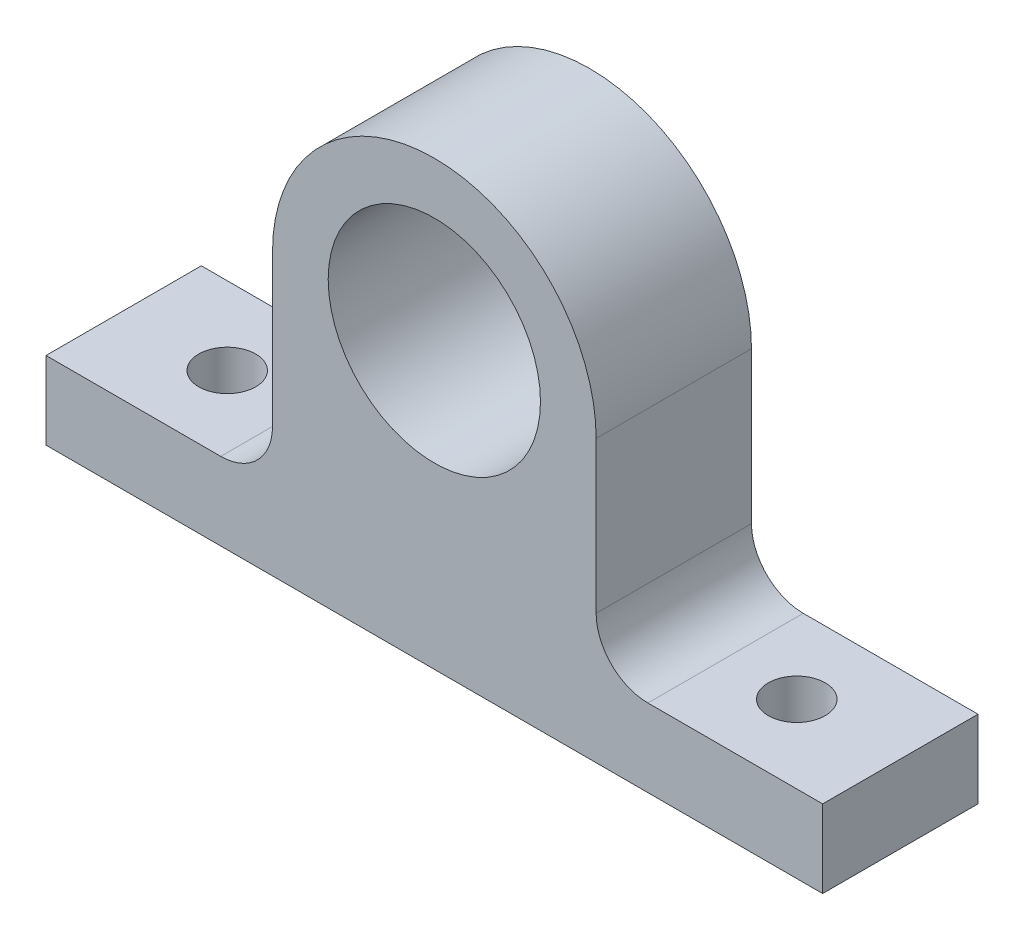
SolidWorks part; units mm, degrees
ref_plane "Front Plane" through (0, 0, 0) normal (0, 0, 1) x (1, 0, 0)
ref_plane "Top Plane" through (0, 0, 0) normal (0, 1, 0) x (1, 0, 0)
ref_plane "Right Plane" through (0, 0, 0) normal (1, 0, 0) x (0, 0, -1)
sketch "Sketch2" plane through (0, 0, 0) normal (0, 0, 1) x (1, 0, 0)
  line L0 (6.25, -8) -> (15, -8)
  line L1 (-6.25, 6.1) -> (6.25, 6.1)
  line L2 (-6.25, 6.1) -> (-6.25, -8)
  line L4 (6.25, 6.1) -> (6.25, -8)
  line L5 (-15, -11) -> (15, -11)
  line L6 (-15, -11) -> (-15, -8)
  line L7 (-15, -8) -> (-6.25, -8)
  line L8 (15, -11) -> (15, -8)
  circle A0 centre (0, 0) radius 4.1
  point P4 (0, 6.1)
  point P5 (0, -11)
  dimension "D1" = 6.1
  dimension "8.2" = 8.2
  dimension "D2" = 30
  dimension "D3" = 3
  dimension "D4" = 12.5
  dimension "D5" = 11
extrude "Boss-Extrude1" add sketch "Sketch2" along normal mid plane 6
fillet "Fillet1" 2 edges at (6.25, 6.1, 0) (-6.25, 6.1, 0) type full round first side face at (6.25, -0.95, 0) second side face at (-6.25, -0.95, 0) middle face at (0, 6.1, 0)
fillet "Fillet2" radius 2 2 edges at (6.25, -8, 0) (-6.25, -8, 0)
sketch "Sketch3" plane through (0, -8, 0) normal (0, 1, 0) x (1, 0, 0)
  line L0 (-15, -3) -> (-15, 3) construction
  line L1 (15, -3) -> (15, 3) construction
  circle A0 centre (-11, 0) radius 1.1
  circle A1 centre (11, 0) radius 1.1
  dimension "D3" = 2.2
  dimension "D1" = 4
  dimension "D2" = 4
extrude "Cut-Extrude1" cut sketch "Sketch3" against normal up to surface (3 mm away) up to face at (0, -11, 0)
